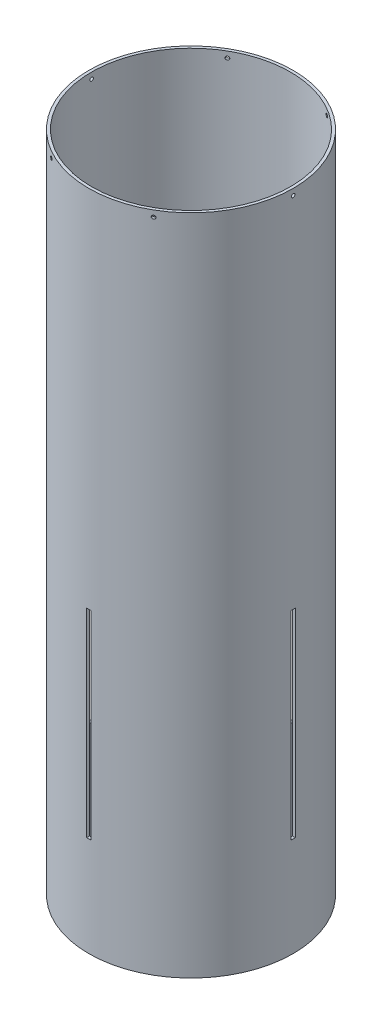
SolidWorks part; units mm, degrees
ref_plane "Front Plane" through (0, 0, 0) normal (0, 0, 1) x (1, 0, 0)
ref_plane "Top Plane" through (0, 0, 0) normal (0, 1, 0) x (1, 0, 0)
ref_plane "Right Plane" through (0, 0, 0) normal (1, 0, 0) x (0, 0, -1)
sketch "Sketch1" plane through (0, 0, 0) normal (0, 1, 0) x (1, 0, 0)
  circle A0 centre (0, 0) radius 76.2
  circle A1 centre (0, 0) radius 78.359
  dimension "D1" = 152.4
  dimension "D2" = 156.718
extrude "Boss-Extrude1" add sketch "Sketch1" along normal blind 508
ref_plane "Plane1" through (0, 0, 0) normal (0.7071, 0, 0.7071) x (0.7071, 0, -0.7071)
ref_axis "Axis1" through (0, 508, 0) along (0, -1, 0)
sketch "Sketch2" plane through (0, 0, 0) normal (1, 0, 0) x (0, 0, -1)
  line L0 (0, 0) -> (0, 76.2)
  line L1 (1.5875, 76.2) -> (-1.5875, 76.2)
  line L2 (1.5875, 76.2) -> (1.5875, 228.6)
  line L3 (1.5875, 228.6) -> (-1.5875, 228.6)
  line L4 (-1.5875, 76.2) -> (-1.5875, 228.6)
  line L5 (1.5875, 76.2) -> (-1.5875, 228.6) construction
  line L6 (1.5875, 228.6) -> (-1.5875, 76.2) construction
  line L7 (78.359, 508) -> (-78.359, 508) construction
  line L8 (78.359, 508) -> (-78.359, 508)
  line L9 (0, 508) -> (0, 503.2375)
  circle A0 centre (0, 503.2375) radius 1.3525
  point P0 (0, 152.4)
  dimension "D4" = 2.7051
  dimension "D1" = 3.175
  dimension "D2" = 152.4
  dimension "D3" = 76.2
  dimension "D5" = 4.7625
extrude "Cut-Extrude1" cut sketch "Sketch2" against normal through all contours L4 L1 L2 L3 region at (0, 152.4, 0)
pattern_circular "CirPattern1" count 4 over 360 about axis through (0, 0, 0) along (0, 1, 0) of "Cut-Extrude1" reverse direction yes
extrude "Cut-Extrude2" cut sketch "Sketch2<3>" against normal through all contours A0 region at (0, 502.3082, 0.9293)
sketch "Sketch2<3>" plane through (0, 0, 0) normal (1, 0, 0) x (0, 0, -1) same geometry as "Sketch2"
pattern_circular "CirPattern2" count 6 over 360 about axis through (0, 508, 0) along (0, -1, 0) of "Cut-Extrude2"
sketch "Sketch3" plane through (0, 0, 0) normal (0.7071, 0, 0.7071) x (0.7071, 0, -0.7071)
  line L0 (0, 0) -> (0, 127) construction
  circle A0 centre (0, 127) radius 3.175
  dimension "D1" = 6.35
  dimension "D2" = 127
extrude "Cut-Extrude3" cut sketch "Sketch3" against normal through all
equation "\"Aft_Lower_Length\"= 20in"
equation "\"D1@Boss-Extrude1\"=\"Aft_Lower_Length\""
equation "\"AB_Coupler_OD_Length\"= .6875in"
equation "\"AB_Coupling_Section_Length\"= 0.375in"
equation "\"AB_Coupler_Length\"= \"AB_Coupler_OD_Length\" + \"AB_Coupling_Section_Length\" * 2"
equation "\"AB_Coupler_Num_Screws\"= 6"
equation "\"AB_Coupling_Screw_Diameter\"= 0.1065in"
equation "\"Aft_Upper_Length\"= \"Aft_Section_Length\" - \"Aft_Lower_Length\" - \"AB_Coupler_OD_Length\""
equation "\"Aft_Section_Length\"= 40in"
equation "\"D4@Sketch2\"=\"AB_Coupling_Screw_Diameter\""
equation "\"D5@Sketch2\"=\"AB_Coupling_Section_Length\"/2"
equation "\"D1@CirPattern2\"=\"AB_Coupler_Num_Screws\""
equation "\"Rail_Nut_From_Bottom\"= 5in"
equation "\"Rail_Nut_Diam\"= 0.25in"
equation "\"D1@Sketch3\"=\"Rail_Nut_Diam\""
equation "\"D2@Sketch3\"=\"Rail_Nut_From_Bottom\""
